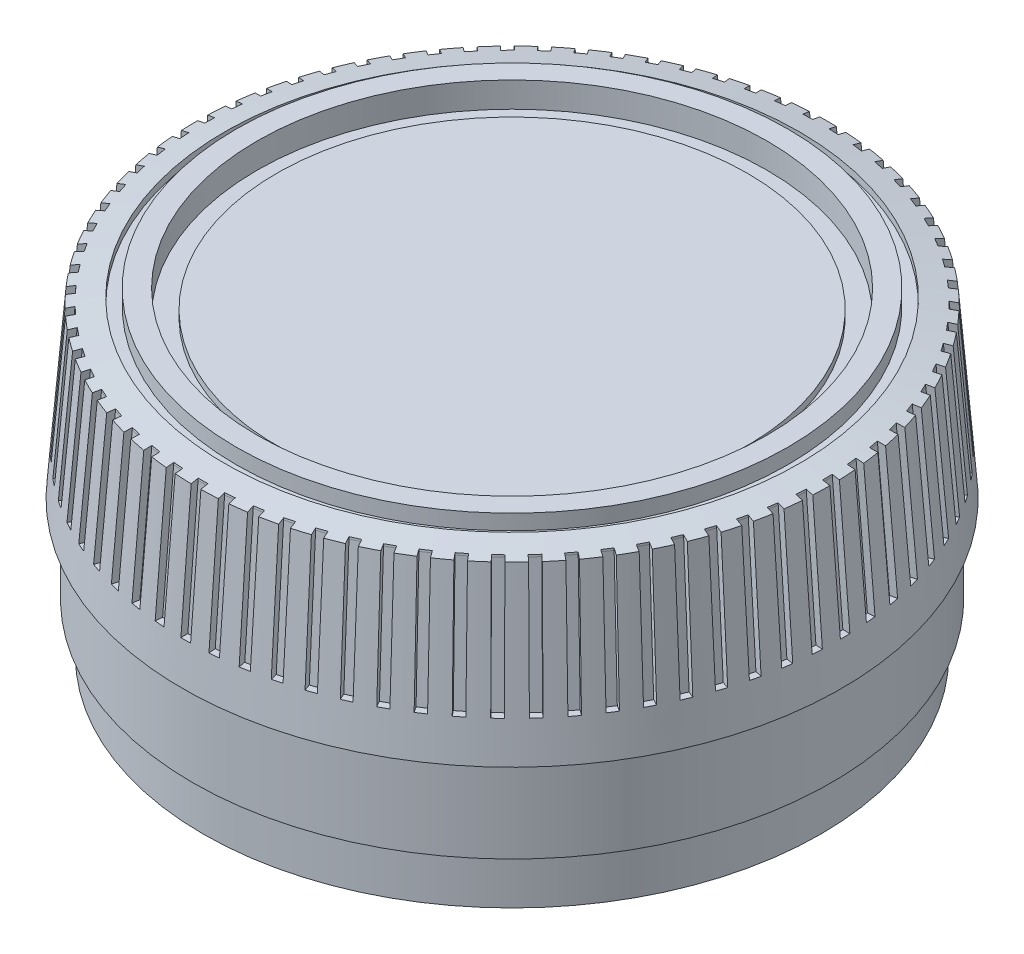
SolidWorks part; units mm, degrees
ref_plane "Front Plane" through (0, 0, 0) normal (0, 0, 1) x (1, 0, 0)
ref_plane "Top Plane" through (0, 0, 0) normal (0, 1, 0) x (1, 0, 0)
ref_plane "Right Plane" through (0, 0, 0) normal (1, 0, 0) x (0, 0, -1)
sketch "Sketch1" plane through (0, 0, 0) normal (1, 0, 0) x (0, 0, -1)
  line L0 (-22.3, 0) -> (-22.3, 3.6)
  line L1 (-22.3, 3.6) -> (-23.065, 3.6)
  line L2 (-23.065, 3.6) -> (-23.065, 9.86)
  line L3 (-23.065, 9.86) -> (-23.8, 9.86)
  line L4 (-23.8, 9.86) -> (-22.825, 22)
  line L5 (-22.825, 22) -> (-20.75, 22.4)
  line L6 (-20.75, 22.4) -> (-20.75, 21.9)
  line L7 (-20.75, 21.9) -> (-19.91, 21.9)
  line L8 (-19.91, 21.9) -> (-19.91, 23)
  line L9 (-19.91, 23) -> (-18.41, 23)
  line L10 (-18.41, 23) -> (-18.41, 21.17)
  line L11 (-18.41, 21.17) -> (-17.01, 21.17)
  line L12 (-17.01, 21.17) -> (-17.01, 21.67)
  line L13 (-17.01, 21.67) -> (0, 21.67)
  line L14 (0, 21.67) -> (0, 19.92)
  line L15 (0, 19.92) -> (-14.75, 19.92)
  line L16 (-14.75, 19.92) -> (-14.75, 18.69)
  line L17 (-14.75, 18.69) -> (-20.855, 18.69)
  line L18 (-20.855, 18.69) -> (-20.855, 0)
  line L19 (-20.855, 0) -> (-22.3, 0)
  line L20 (0, 0) -> (0, 35.9531) construction
  dimension "D1" = 29.5
  dimension "D2" = 41.71
  dimension "D3" = 1.23
  dimension "D4" = 18.69
  dimension "D5" = 44.6
  dimension "D6" = 3.6
  dimension "D7" = 46.13
  dimension "D8" = 9.86
  dimension "D9" = 47.6
  dimension "D10" = 22
  dimension "D11" = 45.65
  dimension "D12" = 41.5
  dimension "D13" = 22.4
  dimension "D14" = 0.84
  dimension "D15" = 0.5
  dimension "D16" = 23
  dimension "D17" = 1.5
  dimension "D18" = 1.4
  dimension "D19" = 1.33
  dimension "D20" = 0.5
revolve "Revolve1" add sketch "Sketch1" angle 360 about L20
sketch "Sketch2" plane through (0, 0, 0) normal (1, 0, 0) x (0, 0, -1)
  line L0 (-22.825, 22) -> (-23.8, 9.86) construction
  line L1 (-22.825, 22) -> (-23.5679, 12.75)
  line L2 (-22.3266, 21.96) -> (-23.0663, 12.75)
  line L3 (-22.825, 22) -> (-22.6547, 22.4662)
  line L4 (-22.6547, 22.4662) -> (-22.2748, 22.4662)
  line L5 (-22.2748, 22.4662) -> (-22.3266, 21.96)
  line L6 (-23.5679, 12.75) -> (-23.0663, 12.75)
  line L7 (22.825, 22) -> (-22.825, 22) construction
  line L8 (-22.825, 22) -> (-23.8, 9.86) construction
  line L9 (-22.3266, 21.96) -> (-23.3016, 9.82) construction
  dimension "D2" = 9.25
  dimension "D1" = 0.5
extrude "Cut-Extrude1" cut sketch "Sketch2" against normal mid plane 0.7
pattern_circular "CirPattern1" count 75 over 360 about axis through (0, 23, 0) along (0, -1, 0) of "Cut-Extrude1"
sketch "Sketch3" plane through (0, 19.92, 0) normal (0, -1, 0) x (1, 0, 0)
  line L0 (-0.65, -0.65) -> (-0.65, -20.8449)
  line L1 (20.8449, 0.65) -> (0.65, 0.65)
  line L3 (20.8449, -0.65) -> (0.65, -0.65)
  line L5 (43.4364, 0.65) -> (-43.4364, -0.65) construction
  line L6 (43.4364, -0.65) -> (-43.4364, 0.65) construction
  line L8 (-0.65, 20.8449) -> (-0.65, 0.65)
  line L10 (0.65, 20.8449) -> (0.65, 0.65)
  line L11 (-0.65, 25.8391) -> (0.65, -25.8391) construction
  line L12 (-0.65, -25.8391) -> (0.65, 25.8391) construction
  line L13 (-0.65, -0.65) -> (-20.8449, -0.65)
  line L14 (0.0164, -0.65) -> (-0.0164, -0.65)
  line L15 (0.65, -0.65) -> (0.65, -20.8449)
  line L16 (0.65, 0.0097) -> (0.65, -0.0097)
  line L17 (0.0164, 0.65) -> (-0.0164, 0.65)
  line L18 (-0.65, 0.65) -> (-20.8449, 0.65)
  line L19 (-0.65, 0.0097) -> (-0.65, -0.0097)
  circle A0 centre (0, 0) radius 20.855 construction
  arc A1 (-20.8449, 0.65) -> (-20.8449, -0.65) centre (0, 0) ccw
  arc A2 (0.65, 20.8449) -> (-0.65, 20.8449) centre (0, 0) ccw
  arc A3 (20.8449, -0.65) -> (20.8449, 0.65) centre (0, 0) ccw
  arc A4 (-0.65, -20.8449) -> (0.65, -20.8449) centre (0, 0) ccw
  dimension "D1" = 1.3
  dimension "D2" = 1.3
extrude "Boss-Extrude1" add sketch "Sketch3" along normal blind 13.25 contours L8 L18 A1 L13 L0 A4 L15 L3 A3 L1 L10 A2
sketch "Sketch4" plane through (0, 19.92, 0) normal (0, -1, 0) x (1, 0, 0)
  circle A0 centre (0, 0) radius 5
  dimension "D1" = 10
extrude "Boss-Extrude2" add sketch "Sketch4" along normal blind 20.1
sketch "Sketch5" plane through (0, -0.18, 0) normal (0, -1, 0) x (1, 0, 0)
  line L0 (1.5497, 2.8225) -> (-2.8225, -1.5497)
  line L1 (-0.65, -4.9576) -> (-0.65, -20.8449) construction
  circle A1 centre (0, 0) radius 5 construction
  circle A2 centre (0, 0) radius 3.22
  arc A3 (-2.8225, -1.5497) -> (1.5497, 2.8225) centre (0, 0) ccw
  dimension "D2" = 4.1
  dimension "D3" = 45
  dimension "D1" = 1.78
extrude "Cut-Extrude2" cut sketch "Sketch5" against normal blind 20.1
